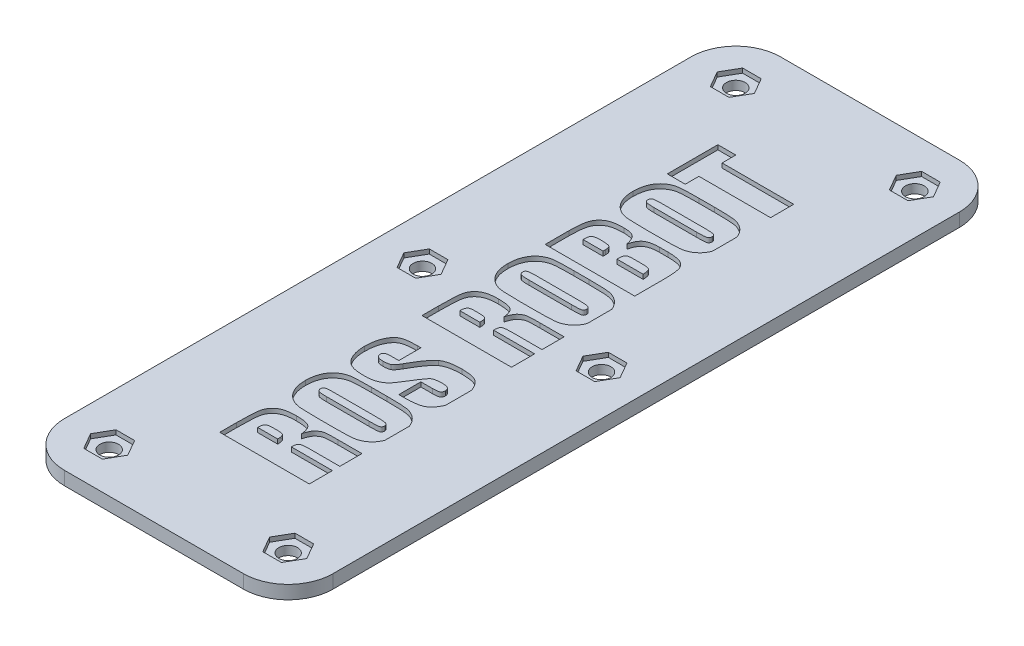
SolidWorks part; units mm, degrees
ref_plane "Front Plane" through (0, 0, 0) normal (0, 0, 1) x (1, 0, 0)
ref_plane "Top Plane" through (0, 0, 0) normal (0, 1, 0) x (1, 0, 0)
ref_plane "Right Plane" through (0, 0, 0) normal (1, 0, 0) x (0, 0, -1)
sketch "Sketch1" plane through (0, 0, 0) normal (0, 1, 0) x (1, 0, 0)
  line L1 (-30, 80) -> (30, 80)
  line L2 (-30, 80) -> (-30, -80)
  line L3 (-30, -80) -> (30, -80)
  line L4 (30, 80) -> (30, -80)
  line L5 (-30, 80) -> (30, -80) construction
  line L6 (-30, -80) -> (30, 80) construction
  point P0 (0, 0)
  dimension "D1" = 60
  dimension "D2" = 160
extrude "Boss-Extrude1" add sketch "Sketch1" along normal blind 3
sketch "Sketch2" plane through (0, 3, 0) normal (0, 1, 0) x (1, 0, 0)
  line L0 (-30, -80) -> (30, -80) construction
  line L2 (-30, 80) -> (-30, -80) construction
  circle A0 centre (-20, -70) radius 2.09
  circle A1 centre (-20, 0) radius 2.09
  circle A2 centre (-20, 70) radius 2.09
  point P6 (0, 0)
  dimension "D1" = 4.18
  dimension "D2" = 70
  dimension "D3" = 70
  dimension "D4" = 10
  dimension "D5" = 10
extrude "Cut-Extrude1" cut sketch "Sketch2" against normal through all
mirror "Mirror1" about plane through (0, 0, 0) normal (1, 0, 0) of "Cut-Extrude1"
sketch "Sketch3" plane through (0, 3, 0) normal (0, 1, 0) x (1, 0, 0)
  line L0 (10, -60) -> (10, 60)
  line L1 (-30, 80) -> (-30, -80) construction
  line L2 (-10, -55.2941) -> (-10, -51.5662)
  line L3 (4.6581, -43.5294) -> (10, -43.5294)
  line L4 (10, -43.5294) -> (10, -48.4706)
  line L5 (10, -48.4706) -> (3.2353, -48.4706)
  line L6 (0.8235, -50.1176) -> (10, -50.1176)
  line L7 (10, -50.1176) -> (10, -55.2941)
  line L8 (10, -55.2941) -> (-10, -55.2941)
  line L9 (-6.7059, -50.1176) -> (-2.2353, -50.1176)
  line L10 (-4.0478, -48.4706) -> (-5.1544, -48.4706)
  line L11 (1.7206, -41.6471) -> (-1.7206, -41.6471)
  line L12 (-1.7206, -29.6471) -> (1.7206, -29.6471)
  line L13 (-4.9596, -36.4706) -> (4.5662, -36.4706)
  line L14 (4.4154, -34.8235) -> (-4.9596, -34.8235)
  line L15 (-3.8824, -16.4706) -> (-3.8824, -21.4118)
  line L16 (-3.8824, -21.4118) -> (-5.4632, -21.4118)
  line L17 (4.0478, -28) -> (2.7059, -28)
  line L18 (2.7059, -28) -> (2.7059, -23.0588)
  line L19 (2.7059, -23.0588) -> (5.2978, -23.0588)
  line L20 (-4.6875, -16.4706) -> (-3.8824, -16.4706)
  line L21 (-10, -10.1176) -> (-10, -6.3897)
  line L22 (4.6581, 1.6471) -> (10, 1.6471)
  line L23 (10, 1.6471) -> (10, -3.2941)
  line L24 (10, -3.2941) -> (3.2353, -3.2941)
  line L25 (0.8235, -4.9412) -> (10, -4.9412)
  line L26 (10, -4.9412) -> (10, -10.1176)
  line L27 (10, -10.1176) -> (-10, -10.1176)
  line L28 (-6.7059, -4.9412) -> (-2.2353, -4.9412)
  line L29 (-4.0478, -3.2941) -> (-5.1544, -3.2941)
  line L30 (1.7206, 3.5294) -> (-1.7206, 3.5294)
  line L31 (-1.7206, 15.5294) -> (1.7206, 15.5294)
  line L32 (-4.9596, 8.7059) -> (4.5662, 8.7059)
  line L33 (4.4154, 10.3529) -> (-4.9596, 10.3529)
  line L34 (-10, 17.4118) -> (-10, 22.7169)
  line L35 (3.364, 29.6471) -> (5.2426, 29.6471)
  line L36 (10, 23.4926) -> (10, 17.4118)
  line L37 (10, 17.4118) -> (-10, 17.4118)
  line L38 (-6.7059, 22.5882) -> (-2.2353, 22.5882)
  line L39 (0.8235, 22.5882) -> (6.7059, 22.5882)
  line L40 (4.7463, 24.4706) -> (2.7831, 24.4706)
  line L41 (1.7206, 31.5294) -> (-1.7206, 31.5294)
  line L42 (-1.7206, 43.5294) -> (1.7206, 43.5294)
  line L43 (-4.9596, 36.7059) -> (4.5662, 36.7059)
  line L44 (4.4154, 38.3529) -> (-4.9596, 38.3529)
  line L45 (-10, 56) -> (-6, 56)
  line L46 (-6, 56) -> (-6, 52.9412)
  line L47 (-6, 52.9412) -> (10, 52.9412)
  line L48 (10, 52.9412) -> (10, 47.7647)
  line L49 (10, 47.7647) -> (-6, 47.7647)
  line L50 (-6, 47.7647) -> (-6, 44.7059)
  line L51 (-6, 44.7059) -> (-10, 44.7059)
  line L52 (-10, 44.7059) -> (-10, 56)
  spline S0 degree 3 poles (-10, -51.5662) (-10.0021, -50.9938) (-9.9925, -50.1738) (-9.9618, -49.131) (-9.9343, -48.4616) (-9.8938, -47.8671) (-9.8469, -47.3485) (-9.7938, -46.9053) (-9.7279, -46.5265) (-9.6422, -46.1927) (-9.5296, -45.8846) (-9.3956, -45.5898) (-9.2282, -45.3117) (-9.0316, -45.0523) (-8.8156, -44.8023) (-8.5646, -44.5748) (-8.2904, -44.3559) (-7.9777, -44.158) (-7.6226, -43.9907) (-7.2263, -43.847) (-6.7869, -43.7305) (-6.3051, -43.6403) (-5.579, -43.5478) (-5.0099, -43.5348) (-4.6176, -43.5294) knots 0 0 0 0 0.148881 0.213303 0.271377 0.323138 0.368276 0.406827 0.439217 0.468212 0.496346 0.524443 0.552325 0.580569 0.609028 0.638128 0.668547 0.700209 0.734143 0.770448 0.80973 0.852244 0.897872 1 1 1 1
  spline S1 degree 3 poles (-4.6176, -43.5294) (-4.2653, -43.5236) (-3.7599, -43.5474) (-3.1182, -43.6025) (-2.7075, -43.671) (-2.3432, -43.7491) (-2.0238, -43.8459) (-1.7543, -43.9676) (-1.5246, -44.1057) (-1.3304, -44.2743) (-1.1605, -44.4757) (-1.0104, -44.7121) (-0.8806, -44.9835) (-0.7776, -45.291) (-0.6464, -45.7633) (-0.5975, -46.1443) (-0.5735, -46.4081) knots 0 0 0 0 0.183844 0.264214 0.336185 0.401092 0.458783 0.510057 0.555172 0.598283 0.643683 0.692329 0.744143 0.800414 0.861431 1 1 1 1
  spline S2 degree 3 poles (-0.5735, -46.4081) (-0.5082, -46.1692) (-0.4158, -45.8227) (-0.2536, -45.3924) (-0.1242, -45.1174) (0.0082, -44.8722) (0.1462, -44.6567) (0.2982, -44.4752) (0.5056, -44.2791) (0.7695, -44.0853) (1.0739, -43.8901) (1.3668, -43.7472) (1.6163, -43.6653) (1.8438, -43.6284) (2.0703, -43.5981) (2.3577, -43.579) (2.7033, -43.5604) (3.1078, -43.5466) (3.7658, -43.5296) (4.2893, -43.5348) (4.6581, -43.5294) knots 0 0 0 0 0.11021 0.159198 0.204304 0.245276 0.283065 0.317885 0.350264 0.409778 0.463156 0.510931 0.554366 0.579275 0.613344 0.655979 0.70728 0.767268 0.835956 1 1 1 1
  spline S3 degree 3 poles (3.2353, -48.4706) (2.989, -48.4726) (2.6391, -48.4726) (2.1993, -48.5048) (1.9269, -48.5332) (1.6924, -48.5693) (1.4957, -48.6105) (1.339, -48.6657) (1.2146, -48.7289) (1.114, -48.8112) (1.0393, -48.9233) (0.9667, -49.0542) (0.9194, -49.2179) (0.8733, -49.4037) (0.8356, -49.7073) (0.824, -49.9481) (0.8235, -50.1176) knots 0 0 0 0 0.208735 0.296167 0.373443 0.440695 0.497113 0.543415 0.581035 0.614932 0.652106 0.694368 0.741317 0.795712 0.856499 1 1 1 1
  spline S4 degree 3 poles (-2.2353, -50.1176) (-2.241, -49.859) (-2.2449, -49.4942) (-2.3595, -49.0703) (-2.4455, -48.8674) (-2.5571, -48.7457) (-2.6702, -48.6674) (-2.8204, -48.6082) (-3.0015, -48.5571) (-3.2158, -48.5182) (-3.5672, -48.4758) (-3.8494, -48.4762) (-4.0478, -48.4706) knots 0 0 0 0 0.26299 0.361623 0.442867 0.481356 0.526611 0.580322 0.643299 0.716254 0.799641 1 1 1 1
  spline S5 degree 3 poles (-5.1544, -48.4706) (-5.4183, -48.4732) (-5.7882, -48.4915) (-6.209, -48.649) (-6.422, -48.8134) (-6.5523, -49.0502) (-6.6913, -49.4796) (-6.7008, -49.8538) (-6.7059, -50.1176) knots 0 0 0 0 0.296724 0.405999 0.497474 0.590179 0.702697 1 1 1 1
  spline S6 degree 3 poles (1.7206, -29.6471) (2.1887, -29.6516) (2.8628, -29.6489) (3.7244, -29.6629) (4.2868, -29.6838) (4.7956, -29.6992) (5.249, -29.7256) (5.6474, -29.7548) (6.1016, -29.7961) (6.625, -29.8819) (7.2194, -30.0688) (7.7848, -30.3319) (8.3184, -30.6676) (8.8126, -31.0692) (9.2459, -31.5466) (9.6203, -32.0876) (9.9272, -32.6949) (10.1748, -33.3563) (10.4086, -34.3407) (10.4749, -35.116) (10.4706, -35.6471) knots 0 0 0 0 0.113101 0.162848 0.208171 0.249056 0.285827 0.31789 0.345554 0.396029 0.44566 0.495598 0.546282 0.597611 0.648955 0.701516 0.75607 0.812935 0.871747 1 1 1 1
  spline S7 degree 3 poles (10.4706, -35.6471) (10.4702, -36.1567) (10.4117, -36.9073) (10.1869, -37.8648) (9.9551, -38.5228) (9.666, -39.1346) (9.2939, -39.6787) (8.8684, -40.1717) (8.3693, -40.5862) (7.8326, -40.9353) (7.2648, -41.2061) (6.6744, -41.4) (6.1562, -41.4954) (5.705, -41.5355) (5.3079, -41.5652) (4.8519, -41.59) (4.3384, -41.6129) (3.766, -41.6259) (2.8873, -41.6415) (2.1985, -41.6458) (1.7206, -41.6471) knots 0 0 0 0 0.123187 0.181008 0.237203 0.291505 0.343988 0.396026 0.44835 0.500181 0.550382 0.599921 0.649928 0.677302 0.709372 0.746151 0.787647 0.833563 0.884505 1 1 1 1
  spline S8 degree 3 poles (-1.7206, -41.6471) (-2.1875, -41.6426) (-2.8616, -41.6453) (-3.7232, -41.6312) (-4.2868, -41.6107) (-4.7942, -41.5935) (-5.2479, -41.5731) (-5.6461, -41.5428) (-6.102, -41.5024) (-6.6245, -41.4108) (-7.2196, -41.2259) (-7.7852, -40.961) (-8.3211, -40.6288) (-8.8141, -40.2235) (-9.2437, -39.7445) (-9.6213, -39.2061) (-9.9283, -38.5999) (-10.1693, -37.9353) (-10.4131, -36.9536) (-10.4652, -36.1757) (-10.4706, -35.6471) knots 0 0 0 0 0.112808 0.162853 0.208178 0.249064 0.285525 0.317884 0.345549 0.396077 0.445709 0.495649 0.546586 0.597688 0.649252 0.701572 0.756128 0.812892 0.872063 1 1 1 1
  spline S9 degree 3 poles (-10.4706, -35.6471) (-10.4714, -35.1372) (-10.4096, -34.3888) (-10.1907, -33.4315) (-9.9597, -32.7739) (-9.664, -32.1639) (-9.2966, -31.6157) (-8.8667, -31.1263) (-8.3697, -30.7111) (-7.8316, -30.3634) (-7.2658, -30.087) (-6.6754, -29.8952) (-6.1588, -29.7978) (-5.7072, -29.7597) (-5.3094, -29.7227) (-4.8517, -29.7062) (-4.3385, -29.6803) (-3.7659, -29.6698) (-2.8875, -29.6434) (-2.1984, -29.6546) (-1.7206, -29.6471) knots 0 0 0 0 0.123194 0.180663 0.236861 0.291296 0.344027 0.395847 0.448174 0.500008 0.55034 0.599882 0.649601 0.676977 0.709367 0.746132 0.787631 0.833549 0.884501 1 1 1 1
  spline S10 degree 3 poles (-4.9596, -34.8235) (-5.1753, -34.8242) (-5.4829, -34.83) (-5.8716, -34.843) (-6.1155, -34.8622) (-6.3276, -34.8839) (-6.5086, -34.9074) (-6.6559, -34.9406) (-6.806, -34.9862) (-6.954, -35.0702) (-7.1431, -35.2687) (-7.1725, -35.486) (-7.1765, -35.6213) knots 0 0 0 0 0.245382 0.350014 0.44228 0.523563 0.592561 0.649714 0.69512 0.770679 0.840726 1 1 1 1
  spline S11 degree 3 poles (-7.1765, -35.6213) (-7.1826, -35.7474) (-7.1389, -35.933) (-7.0007, -36.1393) (-6.8803, -36.2454) (-6.7481, -36.3134) (-6.606, -36.3546) (-6.4264, -36.3903) (-6.2075, -36.4176) (-5.9516, -36.4453) (-5.5307, -36.4612) (-5.1963, -36.473) (-4.9596, -36.4706) knots 0 0 0 0 0.14123 0.20787 0.277368 0.319365 0.374393 0.44345 0.525667 0.62281 0.733417 1 1 1 1
  spline S12 degree 3 poles (4.5662, -36.4706) (4.8346, -36.4661) (5.2158, -36.4689) (5.6951, -36.4552) (5.9902, -36.4341) (6.2432, -36.4194) (6.4541, -36.3928) (6.6225, -36.365) (6.7864, -36.3252) (6.9456, -36.2427) (7.1431, -36.032) (7.1757, -35.8027) (7.1765, -35.6581) knots 0 0 0 0 0.263966 0.37491 0.47152 0.554902 0.624119 0.680394 0.722784 0.789642 0.853612 1 1 1 1
  spline S13 degree 3 poles (7.1765, -35.6581) (7.1748, -35.5096) (7.1356, -35.267) (6.9074, -35.0588) (6.7277, -34.9785) (6.5458, -34.9318) (6.3632, -34.9057) (6.1401, -34.8796) (5.8753, -34.8573) (5.5687, -34.8447) (5.0773, -34.8286) (4.6887, -34.825) (4.4154, -34.8235) knots 0 0 0 0 0.144509 0.209626 0.282207 0.327425 0.385695 0.455209 0.538352 0.635125 0.743353 1 1 1 1
  spline S14 degree 3 poles (-5.4632, -21.4118) (-5.765, -21.4118) (-6.1723, -21.4209) (-6.6458, -21.5046) (-6.8672, -21.593) (-7.0158, -21.7183) (-7.1437, -21.9403) (-7.1819, -22.1356) (-7.1765, -22.2721) knots 0 0 0 0 0.412531 0.554325 0.654756 0.734266 0.814634 1 1 1 1
  spline S15 degree 3 poles (-7.1765, -22.2721) (-7.1753, -22.4224) (-7.1339, -22.6526) (-6.9564, -22.8986) (-6.7779, -23.0494) (-6.5473, -23.1638) (-6.1427, -23.267) (-5.8109, -23.3007) (-5.5735, -23.2941) knots 0 0 0 0 0.212113 0.312859 0.418563 0.535756 0.66915 1 1 1 1
  spline S16 degree 3 poles (-5.5735, -23.2941) (-5.2685, -23.2963) (-4.7355, -23.2666) (-4.2139, -23.1434) (-4.0074, -23.0441) knots 0 0 0 0 0.572651 1 1 1 1
  spline S17 degree 3 poles (-4.0074, -23.0441) (-3.9087, -22.9953) (-3.7635, -22.892) (-3.5783, -22.7165) (-3.4317, -22.5391) (-3.2741, -22.3344) (-3.0492, -21.9996) (-2.8928, -21.7223) (-2.7831, -21.5294) knots 0 0 0 0 0.166753 0.269572 0.387216 0.516182 0.662459 1 1 1 1
  spline S18 degree 3 poles (-2.7831, -21.5294) (-2.4734, -20.9703) (-2.0184, -20.1729) (-1.3881, -19.1897) (-0.9563, -18.5738) (-0.5522, -18.0389) (-0.0677, -17.4805) (0.3024, -17.1194) (0.5662, -16.9375) knots 0 0 0 0 0.335278 0.4813 0.612364 0.729739 0.832713 1 1 1 1
  spline S19 degree 3 poles (0.5662, -16.9375) (0.806, -16.77) (1.2115, -16.5589) (1.8106, -16.3573) (2.3243, -16.226) (2.8906, -16.1237) (3.7446, -16.0244) (4.4137, -16) (4.875, -16) knots 0 0 0 0 0.195997 0.304678 0.423526 0.551406 0.690506 1 1 1 1
  spline S20 degree 3 poles (4.875, -16) (5.2122, -15.9983) (5.6998, -16.0135) (6.3256, -16.0701) (6.7422, -16.1221) (7.1236, -16.1969) (7.469, -16.2838) (7.7801, -16.385) (8.0583, -16.5087) (8.3139, -16.656) (8.557, -16.8277) (8.7858, -17.0338) (9.0067, -17.2654) (9.2179, -17.528) (9.4131, -17.8237) (9.6079, -18.1433) (9.8414, -18.6198) (10.1006, -19.2594) (10.3969, -20.3943) (10.4676, -21.2925) (10.4706, -21.9044) knots 0 0 0 0 0.107325 0.155097 0.199939 0.240858 0.278693 0.313224 0.344823 0.375395 0.406993 0.439316 0.473245 0.508753 0.546395 0.585923 0.627781 0.715119 0.805079 1 1 1 1
  spline S21 degree 3 poles (10.4706, -21.9044) (10.4757, -22.2484) (10.4446, -22.7548) (10.3628, -23.4141) (10.2732, -23.8804) (10.1612, -24.328) (10.0192, -24.7555) (9.8605, -25.1658) (9.6676, -25.5494) (9.4591, -25.9093) (9.2368, -26.2396) (8.9991, -26.5368) (8.7496, -26.8027) (8.4841, -27.0361) (8.2022, -27.235) (7.9096, -27.4062) (7.5968, -27.5388) (7.2633, -27.6501) (6.9011, -27.7452) (6.505, -27.82) (6.0773, -27.8875) (5.616, -27.9373) (4.936, -27.9878) (4.4094, -27.9998) (4.0478, -28) knots 0 0 0 0 0.100148 0.147671 0.19347 0.238417 0.282003 0.324638 0.366476 0.406958 0.44578 0.482362 0.517724 0.551885 0.585175 0.618127 0.650431 0.683967 0.720516 0.759451 0.801367 0.846634 0.894615 1 1 1 1
  spline S22 degree 3 poles (5.2978, -23.0588) (5.4794, -23.0613) (5.7378, -23.049) (6.0657, -23.0335) (6.2711, -23.0047) (6.4517, -22.98) (6.6031, -22.9371) (6.7301, -22.8953) (6.8628, -22.8277) (6.9937, -22.7117) (7.1506, -22.4544) (7.1729, -22.2151) (7.1765, -22.0551) knots 0 0 0 0 0.221449 0.31586 0.400263 0.474516 0.538003 0.591926 0.637412 0.719013 0.801608 1 1 1 1
  spline S23 degree 3 poles (7.1765, -22.0551) (7.1797, -21.8865) (7.1319, -21.6346) (6.944, -21.3618) (6.7516, -21.2047) (6.511, -21.0827) (6.094, -20.9668) (5.75, -20.942) (5.5074, -20.9412) knots 0 0 0 0 0.223439 0.325747 0.431377 0.547858 0.679404 1 1 1 1
  spline S24 degree 3 poles (5.5074, -20.9412) (5.2301, -20.9407) (4.8335, -20.9536) (4.3315, -21.0008) (4.0144, -21.0585) (3.7334, -21.12) (3.4321, -21.228) (3.2311, -21.3302) (3.125, -21.4228) knots 0 0 0 0 0.33668 0.481833 0.611779 0.728037 0.830669 1 1 1 1
  spline S25 degree 3 poles (3.125, -21.4228) (3.0067, -21.5278) (2.832, -21.7237) (2.5986, -22.0274) (2.3862, -22.3232) (2.1458, -22.6637) (1.7857, -23.219) (1.5142, -23.6656) (1.3235, -23.9779) knots 0 0 0 0 0.151179 0.250673 0.366592 0.499698 0.649697 1 1 1 1
  spline S26 degree 3 poles (1.3235, -23.9779) (1.1312, -24.2944) (0.8539, -24.7471) (0.4867, -25.3154) (0.2465, -25.6779) (0.024, -25.9952) (-0.1732, -26.2708) (-0.3489, -26.5042) (-0.5602, -26.7562) (-0.8385, -27.0321) (-1.2198, -27.322) (-1.6571, -27.5826) (-2.1499, -27.8167) (-2.7079, -28.0109) (-3.5918, -28.187) (-4.2954, -28.2419) (-4.7868, -28.2353) knots 0 0 0 0 0.139506 0.199942 0.254867 0.303273 0.345934 0.382495 0.413289 0.469759 0.52968 0.593251 0.661185 0.734906 0.815121 1 1 1 1
  spline S27 degree 3 poles (-4.7868, -28.2353) (-5.1483, -28.2299) (-5.6721, -28.2229) (-6.342, -28.1555) (-6.7866, -28.0911) (-7.1929, -28.0062) (-7.5618, -27.9063) (-7.8893, -27.7803) (-8.183, -27.6392) (-8.4486, -27.4744) (-8.6932, -27.2854) (-8.9296, -27.0793) (-9.1431, -26.8428) (-9.3479, -26.5869) (-9.5388, -26.3089) (-9.711, -26.0053) (-9.9259, -25.5665) (-10.1466, -24.9651) (-10.4114, -23.8851) (-10.4702, -23.0241) (-10.4706, -22.4338) knots 0 0 0 0 0.115094 0.16642 0.214115 0.25793 0.298418 0.335563 0.369391 0.401957 0.434786 0.46765 0.501588 0.535991 0.571894 0.608743 0.64693 0.727243 0.81197 1 1 1 1
  spline S28 degree 3 poles (-10.4706, -22.4338) (-10.4681, -22.0991) (-10.4534, -21.6059) (-10.3832, -20.9641) (-10.3105, -20.511) (-10.2136, -20.0772) (-10.102, -19.6612) (-9.9641, -19.2668) (-9.8111, -18.8916) (-9.6395, -18.5421) (-9.457, -18.2203) (-9.2585, -17.9336) (-9.0613, -17.6686) (-8.8392, -17.446) (-8.617, -17.2428) (-8.377, -17.0786) (-8.1223, -16.9405) (-7.8384, -16.8309) (-7.5198, -16.7307) (-7.1549, -16.6529) (-6.7482, -16.5815) (-6.2949, -16.5328) (-5.6039, -16.4819) (-5.0626, -16.471) (-4.6875, -16.4706) knots 0 0 0 0 0.103075 0.151642 0.198646 0.244222 0.288419 0.331123 0.37273 0.413047 0.450895 0.486465 0.520341 0.552351 0.583079 0.612899 0.641587 0.672056 0.706415 0.744299 0.786776 0.83347 0.88453 1 1 1 1
  spline S29 degree 3 poles (-10, -6.3897) (-10.0021, -5.8173) (-9.9925, -4.9973) (-9.9618, -3.9545) (-9.9343, -3.2851) (-9.8938, -2.6907) (-9.8469, -2.172) (-9.7938, -1.7288) (-9.7279, -1.3501) (-9.6422, -1.0162) (-9.5296, -0.7081) (-9.3956, -0.4133) (-9.2282, -0.1353) (-9.0316, 0.1241) (-8.8156, 0.3741) (-8.5646, 0.6016) (-8.2904, 0.8205) (-7.9777, 1.0184) (-7.6226, 1.1858) (-7.2263, 1.3294) (-6.7869, 1.4459) (-6.3051, 1.5362) (-5.579, 1.6287) (-5.0099, 1.6416) (-4.6176, 1.6471) knots 0 0 0 0 0.148881 0.213303 0.271377 0.323138 0.368276 0.406827 0.439217 0.468212 0.496346 0.524443 0.552325 0.580569 0.609028 0.638128 0.668547 0.700209 0.734143 0.770448 0.80973 0.852244 0.897872 1 1 1 1
  spline S30 degree 3 poles (-4.6176, 1.6471) (-4.2653, 1.6529) (-3.7599, 1.629) (-3.1182, 1.574) (-2.7075, 1.5055) (-2.3432, 1.4273) (-2.0238, 1.3305) (-1.7543, 1.2089) (-1.5246, 1.0707) (-1.3304, 0.9022) (-1.1605, 0.7008) (-1.0104, 0.4644) (-0.8806, 0.1929) (-0.7776, -0.1145) (-0.6464, -0.5869) (-0.5975, -0.9678) (-0.5735, -1.2316) knots 0 0 0 0 0.183844 0.264214 0.336185 0.401092 0.458783 0.510057 0.555172 0.598283 0.643683 0.692329 0.744143 0.800414 0.861431 1 1 1 1
  spline S31 degree 3 poles (-0.5735, -1.2316) (-0.5082, -0.9927) (-0.4158, -0.6463) (-0.2536, -0.216) (-0.1242, 0.0591) (0.0082, 0.3043) (0.1462, 0.5197) (0.2982, 0.7013) (0.5056, 0.8974) (0.7695, 1.0911) (1.0739, 1.2863) (1.3668, 1.4293) (1.6163, 1.5112) (1.8438, 1.5481) (2.0703, 1.5783) (2.3577, 1.5974) (2.7033, 1.6161) (3.1078, 1.6299) (3.7658, 1.6469) (4.2893, 1.6416) (4.6581, 1.6471) knots 0 0 0 0 0.11021 0.159198 0.204304 0.245276 0.283065 0.317885 0.350264 0.409778 0.463156 0.510931 0.554366 0.579275 0.613344 0.655979 0.70728 0.767268 0.835956 1 1 1 1
  spline S32 degree 3 poles (3.2353, -3.2941) (2.989, -3.2962) (2.6391, -3.2961) (2.1993, -3.3283) (1.9269, -3.3567) (1.6924, -3.3928) (1.4957, -3.4341) (1.339, -3.4893) (1.2146, -3.5525) (1.114, -3.6348) (1.0393, -3.7469) (0.9667, -3.8778) (0.9194, -4.0414) (0.8733, -4.2272) (0.8356, -4.5308) (0.824, -4.7717) (0.8235, -4.9412) knots 0 0 0 0 0.208735 0.296167 0.373443 0.440695 0.497113 0.543415 0.581035 0.614932 0.652106 0.694368 0.741317 0.795712 0.856499 1 1 1 1
  spline S33 degree 3 poles (-2.2353, -4.9412) (-2.241, -4.6826) (-2.2449, -4.3177) (-2.3595, -3.8938) (-2.4455, -3.6909) (-2.5571, -3.5692) (-2.6702, -3.491) (-2.8204, -3.4317) (-3.0015, -3.3807) (-3.2158, -3.3417) (-3.5672, -3.2993) (-3.8494, -3.2997) (-4.0478, -3.2941) knots 0 0 0 0 0.26299 0.361623 0.442867 0.481356 0.526611 0.580322 0.643299 0.716254 0.799641 1 1 1 1
  spline S34 degree 3 poles (-5.1544, -3.2941) (-5.4183, -3.2968) (-5.7882, -3.315) (-6.209, -3.4725) (-6.422, -3.6369) (-6.5523, -3.8737) (-6.6913, -4.3032) (-6.7008, -4.6773) (-6.7059, -4.9412) knots 0 0 0 0 0.296724 0.405999 0.497474 0.590179 0.702697 1 1 1 1
  spline S35 degree 3 poles (1.7206, 15.5294) (2.1887, 15.5249) (2.8628, 15.5276) (3.7244, 15.5136) (4.2868, 15.4926) (4.7956, 15.4773) (5.249, 15.4509) (5.6474, 15.4217) (6.1016, 15.3804) (6.625, 15.2946) (7.2194, 15.1077) (7.7848, 14.8446) (8.3184, 14.5089) (8.8126, 14.1073) (9.2459, 13.6298) (9.6203, 13.0889) (9.9272, 12.4816) (10.1748, 11.8202) (10.4086, 10.8357) (10.4749, 10.0605) (10.4706, 9.5294) knots 0 0 0 0 0.113101 0.162848 0.208171 0.249056 0.285827 0.31789 0.345554 0.396029 0.44566 0.495598 0.546282 0.597611 0.648955 0.701516 0.75607 0.812935 0.871747 1 1 1 1
  spline S36 degree 3 poles (10.4706, 9.5294) (10.4702, 9.0198) (10.4117, 8.2692) (10.1869, 7.3116) (9.9551, 6.6537) (9.666, 6.0419) (9.2939, 5.4977) (8.8684, 5.0048) (8.3693, 4.5903) (7.8326, 4.2412) (7.2648, 3.9704) (6.6744, 3.7764) (6.1562, 3.681) (5.705, 3.6409) (5.3079, 3.6113) (4.8519, 3.5865) (4.3384, 3.5636) (3.766, 3.5505) (2.8873, 3.535) (2.1985, 3.5307) (1.7206, 3.5294) knots 0 0 0 0 0.123187 0.181008 0.237203 0.291505 0.343988 0.396026 0.44835 0.500181 0.550382 0.599921 0.649928 0.677302 0.709372 0.746151 0.787647 0.833563 0.884505 1 1 1 1
  spline S37 degree 3 poles (-1.7206, 3.5294) (-2.1875, 3.5339) (-2.8616, 3.5312) (-3.7232, 3.5453) (-4.2868, 3.5657) (-4.7942, 3.5829) (-5.2479, 3.6034) (-5.6461, 3.6337) (-6.102, 3.674) (-6.6245, 3.7656) (-7.2196, 3.9505) (-7.7852, 4.2155) (-8.3211, 4.5477) (-8.8141, 4.953) (-9.2437, 5.432) (-9.6213, 5.9703) (-9.9283, 6.5765) (-10.1693, 7.2411) (-10.4131, 8.2229) (-10.4652, 9.0008) (-10.4706, 9.5294) knots 0 0 0 0 0.112808 0.162853 0.208178 0.249064 0.285525 0.317884 0.345549 0.396077 0.445709 0.495649 0.546586 0.597688 0.649252 0.701572 0.756128 0.812892 0.872063 1 1 1 1
  spline S38 degree 3 poles (-10.4706, 9.5294) (-10.4714, 10.0393) (-10.4096, 10.7877) (-10.1907, 11.7449) (-9.9597, 12.4026) (-9.664, 13.0126) (-9.2966, 13.5607) (-8.8667, 14.0501) (-8.3697, 14.4654) (-7.8316, 14.813) (-7.2658, 15.0895) (-6.6754, 15.2813) (-6.1588, 15.3787) (-5.7072, 15.4167) (-5.3094, 15.4538) (-4.8517, 15.4703) (-4.3385, 15.4962) (-3.7659, 15.5067) (-2.8875, 15.5331) (-2.1984, 15.5218) (-1.7206, 15.5294) knots 0 0 0 0 0.123194 0.180663 0.236861 0.291296 0.344027 0.395847 0.448174 0.500008 0.55034 0.599882 0.649601 0.676977 0.709367 0.746132 0.787631 0.833549 0.884501 1 1 1 1
  spline S39 degree 3 poles (-4.9596, 10.3529) (-5.1753, 10.3523) (-5.4829, 10.3464) (-5.8716, 10.3334) (-6.1155, 10.3143) (-6.3276, 10.2926) (-6.5086, 10.2691) (-6.6559, 10.2359) (-6.806, 10.1902) (-6.954, 10.1063) (-7.1431, 9.9078) (-7.1725, 9.6905) (-7.1765, 9.5551) knots 0 0 0 0 0.245382 0.350014 0.44228 0.523563 0.592561 0.649714 0.69512 0.770679 0.840726 1 1 1 1
  spline S40 degree 3 poles (-7.1765, 9.5551) (-7.1826, 9.4291) (-7.1389, 9.2435) (-7.0007, 9.0372) (-6.8803, 8.931) (-6.7481, 8.8631) (-6.606, 8.8219) (-6.4264, 8.7862) (-6.2075, 8.7588) (-5.9516, 8.7312) (-5.5307, 8.7153) (-5.1963, 8.7035) (-4.9596, 8.7059) knots 0 0 0 0 0.14123 0.20787 0.277368 0.319365 0.374393 0.44345 0.525667 0.62281 0.733417 1 1 1 1
  spline S41 degree 3 poles (4.5662, 8.7059) (4.8346, 8.7104) (5.2158, 8.7076) (5.6951, 8.7213) (5.9902, 8.7424) (6.2432, 8.7571) (6.4541, 8.7836) (6.6225, 8.8115) (6.7864, 8.8513) (6.9456, 8.9338) (7.1431, 9.1444) (7.1757, 9.3737) (7.1765, 9.5184) knots 0 0 0 0 0.263966 0.37491 0.47152 0.554902 0.624119 0.680394 0.722784 0.789642 0.853612 1 1 1 1
  spline S42 degree 3 poles (7.1765, 9.5184) (7.1748, 9.6669) (7.1356, 9.9095) (6.9074, 10.1176) (6.7277, 10.198) (6.5458, 10.2447) (6.3632, 10.2708) (6.1401, 10.2969) (5.8753, 10.3191) (5.5687, 10.3318) (5.0773, 10.3479) (4.6887, 10.3515) (4.4154, 10.3529) knots 0 0 0 0 0.144509 0.209626 0.282207 0.327425 0.385695 0.455209 0.538352 0.635125 0.743353 1 1 1 1
  spline S43 degree 3 poles (-10, 22.7169) (-9.9955, 23.1103) (-9.9921, 23.6819) (-9.9527, 24.4186) (-9.9071, 24.9135) (-9.857, 25.3711) (-9.7961, 25.7911) (-9.7188, 26.1725) (-9.6309, 26.5207) (-9.5237, 26.8424) (-9.3912, 27.1434) (-9.2355, 27.4283) (-9.0587, 27.6987) (-8.8552, 27.9531) (-8.6276, 28.1917) (-8.375, 28.4137) (-8.0977, 28.6217) (-7.7862, 28.8126) (-7.4301, 28.9734) (-7.0293, 29.1081) (-6.5873, 29.2218) (-6.1, 29.3043) (-5.3665, 29.3894) (-4.791, 29.4161) (-4.3934, 29.4118) knots 0 0 0 0 0.114375 0.166108 0.21439 0.258844 0.299904 0.337701 0.371916 0.404248 0.43615 0.467396 0.498519 0.529953 0.561953 0.594259 0.627603 0.66261 0.70023 0.740899 0.785396 0.832777 0.884431 1 1 1 1
  spline S44 degree 3 poles (-4.3934, 29.4118) (-4.127, 29.416) (-3.7431, 29.3962) (-3.2561, 29.335) (-2.9376, 29.2799) (-2.6536, 29.1963) (-2.3989, 29.1046) (-2.1784, 28.9884) (-1.985, 28.8544) (-1.8163, 28.6891) (-1.6558, 28.4982) (-1.5162, 28.2669) (-1.3783, 28.0074) (-1.2489, 27.7134) (-1.0963, 27.2527) (-0.9938, 26.8887) (-0.9412, 26.6324) knots 0 0 0 0 0.159635 0.229972 0.294227 0.35305 0.407212 0.456169 0.502024 0.547743 0.597307 0.65111 0.709269 0.77341 0.843331 1 1 1 1
  spline S45 degree 3 poles (-0.9412, 26.6324) (-0.8783, 26.9064) (-0.7658, 27.3007) (-0.5629, 27.7876) (-0.4027, 28.1069) (-0.2205, 28.3873) (-0.0268, 28.6367) (0.1878, 28.8487) (0.4252, 29.025) (0.6872, 29.1721) (0.9755, 29.3025) (1.2968, 29.4066) (1.6481, 29.495) (2.0311, 29.565) (2.6061, 29.6282) (3.0548, 29.6461) (3.364, 29.6471) knots 0 0 0 0 0.144043 0.209309 0.269932 0.32668 0.380292 0.431325 0.480651 0.531247 0.584899 0.64245 0.703941 0.770287 0.841669 1 1 1 1
  spline S46 degree 3 poles (5.2426, 29.6471) (5.5626, 29.6468) (6.0268, 29.6352) (6.6234, 29.5846) (7.0212, 29.535) (7.3857, 29.4682) (7.7163, 29.3886) (8.0154, 29.2938) (8.3632, 29.1496) (8.7467, 28.9274) (9.131, 28.5817) (9.4335, 28.1642) (9.6212, 27.7575) (9.7292, 27.3755) (9.8021, 27.0179) (9.8619, 26.5942) (9.9131, 26.1025) (9.9518, 25.5458) (9.9944, 24.6684) (9.9944, 23.9766) (10, 23.4926) knots 0 0 0 0 0.102269 0.148253 0.191288 0.230306 0.266588 0.299901 0.330446 0.386794 0.440584 0.494395 0.550463 0.582684 0.621084 0.666995 0.719365 0.779044 0.845298 1 1 1 1
  spline S47 degree 2 poles (-2.2353, 22.5882) (-2.243, 22.875) (-2.2463, 23.1618) knots 0 0 0 1 1 1
  spline S48 degree 3 poles (-2.2463, 23.1618) (-2.2431, 23.394) (-2.2711, 23.7204) (-2.4403, 24.0836) (-2.5925, 24.231) (-2.7527, 24.3011) (-2.9141, 24.3494) (-3.1208, 24.3814) (-3.3706, 24.4159) (-3.6639, 24.4398) (-4.143, 24.4659) (-4.5245, 24.4702) (-4.7941, 24.4706) knots 0 0 0 0 0.207117 0.283923 0.350831 0.389245 0.438074 0.499907 0.574465 0.661754 0.760817 1 1 1 1
  spline S49 degree 3 poles (-4.7941, 24.4706) (-5.0622, 24.4736) (-5.4312, 24.4547) (-5.8749, 24.3777) (-6.1089, 24.2909) (-6.2879, 24.1851) (-6.4274, 24.0656) (-6.5346, 23.9321) (-6.6046, 23.7711) (-6.647, 23.5692) (-6.6936, 23.172) (-6.7017, 22.8358) (-6.7059, 22.5882) knots 0 0 0 0 0.246774 0.340005 0.413619 0.475395 0.530632 0.582131 0.631661 0.690822 0.771636 1 1 1 1
  spline S50 degree 3 poles (6.7059, 22.5882) (6.6974, 22.7721) (6.6865, 23.0359) (6.639, 23.3661) (6.6004, 23.5743) (6.5485, 23.7547) (6.4911, 23.9092) (6.4263, 24.0376) (6.3453, 24.1395) (6.2425, 24.2198) (6.117, 24.2905) (5.959, 24.3424) (5.774, 24.3915) (5.5585, 24.4261) (5.2129, 24.4608) (4.9391, 24.4751) (4.7463, 24.4706) knots 0 0 0 0 0.168584 0.241049 0.305039 0.362178 0.412572 0.455707 0.493181 0.530655 0.574326 0.624331 0.682257 0.749354 0.823771 1 1 1 1
  spline S51 degree 3 poles (2.7831, 24.4706) (2.581, 24.4703) (2.2917, 24.4675) (1.9312, 24.4278) (1.7075, 24.4033) (1.5202, 24.3573) (1.3632, 24.3087) (1.2402, 24.2464) (1.1435, 24.1736) (1.0733, 24.0756) (1.0165, 23.953) (0.9652, 23.8) (0.9227, 23.6164) (0.8865, 23.4028) (0.8455, 23.0574) (0.8306, 22.7821) (0.8235, 22.5882) knots 0 0 0 0 0.182344 0.260037 0.326886 0.384748 0.433642 0.474638 0.508444 0.541576 0.582078 0.629925 0.686713 0.751712 0.825136 1 1 1 1
  spline S52 degree 3 poles (1.7206, 43.5294) (2.1887, 43.5249) (2.8628, 43.5276) (3.7244, 43.5136) (4.2868, 43.4926) (4.7956, 43.4773) (5.249, 43.4509) (5.6474, 43.4217) (6.1016, 43.3804) (6.625, 43.2946) (7.2194, 43.1077) (7.7848, 42.8446) (8.3184, 42.5089) (8.8126, 42.1073) (9.2459, 41.6298) (9.6203, 41.0889) (9.9272, 40.4816) (10.1748, 39.8202) (10.4086, 38.8357) (10.4749, 38.0605) (10.4706, 37.5294) knots 0 0 0 0 0.113101 0.162848 0.208171 0.249056 0.285827 0.31789 0.345554 0.396029 0.44566 0.495598 0.546282 0.597611 0.648955 0.701516 0.75607 0.812935 0.871747 1 1 1 1
  spline S53 degree 3 poles (10.4706, 37.5294) (10.4702, 37.0198) (10.4117, 36.2692) (10.1869, 35.3116) (9.9551, 34.6537) (9.666, 34.0419) (9.2939, 33.4977) (8.8684, 33.0048) (8.3693, 32.5903) (7.8326, 32.2412) (7.2648, 31.9704) (6.6744, 31.7764) (6.1562, 31.681) (5.705, 31.6409) (5.3079, 31.6113) (4.8519, 31.5865) (4.3384, 31.5636) (3.766, 31.5505) (2.8873, 31.535) (2.1985, 31.5307) (1.7206, 31.5294) knots 0 0 0 0 0.123187 0.181008 0.237203 0.291505 0.343988 0.396026 0.44835 0.500181 0.550382 0.599921 0.649928 0.677302 0.709372 0.746151 0.787647 0.833563 0.884505 1 1 1 1
  spline S54 degree 3 poles (-1.7206, 31.5294) (-2.1875, 31.5339) (-2.8616, 31.5312) (-3.7232, 31.5453) (-4.2868, 31.5657) (-4.7942, 31.5829) (-5.2479, 31.6034) (-5.6461, 31.6337) (-6.102, 31.674) (-6.6245, 31.7656) (-7.2196, 31.9505) (-7.7852, 32.2155) (-8.3211, 32.5477) (-8.8141, 32.953) (-9.2437, 33.432) (-9.6213, 33.9703) (-9.9283, 34.5765) (-10.1693, 35.2411) (-10.4131, 36.2229) (-10.4652, 37.0008) (-10.4706, 37.5294) knots 0 0 0 0 0.112808 0.162853 0.208178 0.249064 0.285525 0.317884 0.345549 0.396077 0.445709 0.495649 0.546586 0.597688 0.649252 0.701572 0.756128 0.812892 0.872063 1 1 1 1
  spline S55 degree 3 poles (-10.4706, 37.5294) (-10.4714, 38.0393) (-10.4096, 38.7877) (-10.1907, 39.7449) (-9.9597, 40.4026) (-9.664, 41.0126) (-9.2966, 41.5607) (-8.8667, 42.0501) (-8.3697, 42.4654) (-7.8316, 42.813) (-7.2658, 43.0895) (-6.6754, 43.2813) (-6.1588, 43.3787) (-5.7072, 43.4167) (-5.3094, 43.4538) (-4.8517, 43.4703) (-4.3385, 43.4962) (-3.7659, 43.5067) (-2.8875, 43.5331) (-2.1984, 43.5218) (-1.7206, 43.5294) knots 0 0 0 0 0.123194 0.180663 0.236861 0.291296 0.344027 0.395847 0.448174 0.500008 0.55034 0.599882 0.649601 0.676977 0.709367 0.746132 0.787631 0.833549 0.884501 1 1 1 1
  spline S56 degree 3 poles (-4.9596, 38.3529) (-5.1753, 38.3523) (-5.4829, 38.3464) (-5.8716, 38.3334) (-6.1155, 38.3143) (-6.3276, 38.2926) (-6.5086, 38.2691) (-6.6559, 38.2359) (-6.806, 38.1902) (-6.954, 38.1063) (-7.1431, 37.9078) (-7.1725, 37.6905) (-7.1765, 37.5551) knots 0 0 0 0 0.245382 0.350014 0.44228 0.523563 0.592561 0.649714 0.69512 0.770679 0.840726 1 1 1 1
  spline S57 degree 3 poles (-7.1765, 37.5551) (-7.1826, 37.4291) (-7.1389, 37.2435) (-7.0007, 37.0372) (-6.8803, 36.931) (-6.7481, 36.8631) (-6.606, 36.8219) (-6.4264, 36.7862) (-6.2075, 36.7588) (-5.9516, 36.7312) (-5.5307, 36.7153) (-5.1963, 36.7035) (-4.9596, 36.7059) knots 0 0 0 0 0.14123 0.20787 0.277368 0.319365 0.374393 0.44345 0.525667 0.62281 0.733417 1 1 1 1
  spline S58 degree 3 poles (4.5662, 36.7059) (4.8346, 36.7104) (5.2158, 36.7076) (5.6951, 36.7213) (5.9902, 36.7424) (6.2432, 36.7571) (6.4541, 36.7836) (6.6225, 36.8115) (6.7864, 36.8513) (6.9456, 36.9338) (7.1431, 37.1444) (7.1757, 37.3737) (7.1765, 37.5184) knots 0 0 0 0 0.263966 0.37491 0.47152 0.554902 0.624119 0.680394 0.722784 0.789642 0.853612 1 1 1 1
  spline S59 degree 3 poles (7.1765, 37.5184) (7.1748, 37.6669) (7.1356, 37.9095) (6.9074, 38.1176) (6.7277, 38.198) (6.5458, 38.2447) (6.3632, 38.2708) (6.1401, 38.2969) (5.8753, 38.3191) (5.5687, 38.3318) (5.0773, 38.3479) (4.6887, 38.3515) (4.4154, 38.3529) knots 0 0 0 0 0.144509 0.209626 0.282207 0.327425 0.385695 0.455209 0.538352 0.635125 0.743353 1 1 1 1
  point P5 (-30, 0)
  point P6 (10, 0)
  dimension "D1" = 120
  dimension "D2" = 10
extrude "Cut-Extrude2" cut sketch "Sketch3" against normal blind 1 contours S3 L5 L0 L3 S2 S1 S0 L2 L8 L6 S5 L10 S4 L9 | S9 S8 L11 S7 L0 S6 L12 S13 S12 L13 S11 S10 L14 | S28 S27 S26 S25 S24 S23 S22 L19 L18 L17 S21 L0 S20 S19 S18 S17 S16 S15 S14 L16 L15 L20 | S32 L24 L0 L22 S31 S30 S29 L21 L27 L25 S34 L29 S33 L28 | S38 S37 L30 S36 L0 S35 L31 S42 S41 L32 S40 S39 L33 | S46 L35 S45 S44 S43 L34 L37 L0 S51 L40 S50 L39 S49 S48 S47 L38 | S55 S54 L41 S53 L0 S52 L42 S59 S58 L43 S57 S56 L44 | L52 L51 L50 L49 L0 L47 L46 L45 region at (-0.0506, 3, 49.6197) region at (-1.5294, 3, -50.3529) region at (6.4747, 3, -31.9872) region at (0.1248, 3, -23.1918) region at (6.4747, 3, -3.9872) region at (-0.0506, 3, 4.4433) region at (-0.0445, 3, 22.1813) region at (6.4747, 3, 41.1893)
fillet "Fillet1" radius 10 4 edges at (-30, 1.5, -80) (30, 1.5, -80) (30, 1.5, 80) (-30, 1.5, 80)
sketch "Sketch4" plane through (0, 3, 0) normal (0, 1, 0) x (1, 0, 0)
  line L0 (-20, -80) -> (20, -80) construction
  line L1 (24.1569, -70) -> (22.0785, -66.4)
  line L2 (22.0785, -66.4) -> (17.9215, -66.4)
  line L3 (17.9215, -66.4) -> (15.8431, -70)
  line L4 (15.8431, -70) -> (17.9215, -73.6)
  line L5 (17.9215, -73.6) -> (22.0785, -73.6)
  line L6 (22.0785, -73.6) -> (24.1569, -70)
  line L7 (24.1569, 0) -> (22.0785, 3.6)
  line L8 (22.0785, 3.6) -> (17.9215, 3.6)
  line L9 (17.9215, 3.6) -> (15.8431, 0)
  line L10 (15.8431, 0) -> (17.9215, -3.6)
  line L11 (17.9215, -3.6) -> (22.0785, -3.6)
  line L12 (22.0785, -3.6) -> (24.1569, 0)
  line L13 (24.1569, 70) -> (22.0785, 73.6)
  line L14 (22.0785, 73.6) -> (17.9215, 73.6)
  line L15 (17.9215, 73.6) -> (15.8431, 70)
  line L16 (15.8431, 70) -> (17.9215, 66.4)
  line L17 (17.9215, 66.4) -> (22.0785, 66.4)
  line L18 (22.0785, 66.4) -> (24.1569, 70)
  circle A0 centre (20, -70) radius 3.6 construction
  circle A1 centre (20, 0) radius 3.6 construction
  circle A2 centre (20, 70) radius 3.6 construction
  circle A3 centre (20, -70) radius 2.09 construction
  circle A4 centre (20, 0) radius 2.09 construction
  circle A5 centre (20, 70) radius 2.09 construction
  point P35 (20, -66.4)
  dimension "D1" = 7.2
extrude "Cut-Extrude3" cut sketch "Sketch4" against normal blind 1
mirror "Mirror2" about plane through (0, 0, 0) normal (1, 0, 0) of "Cut-Extrude3"
